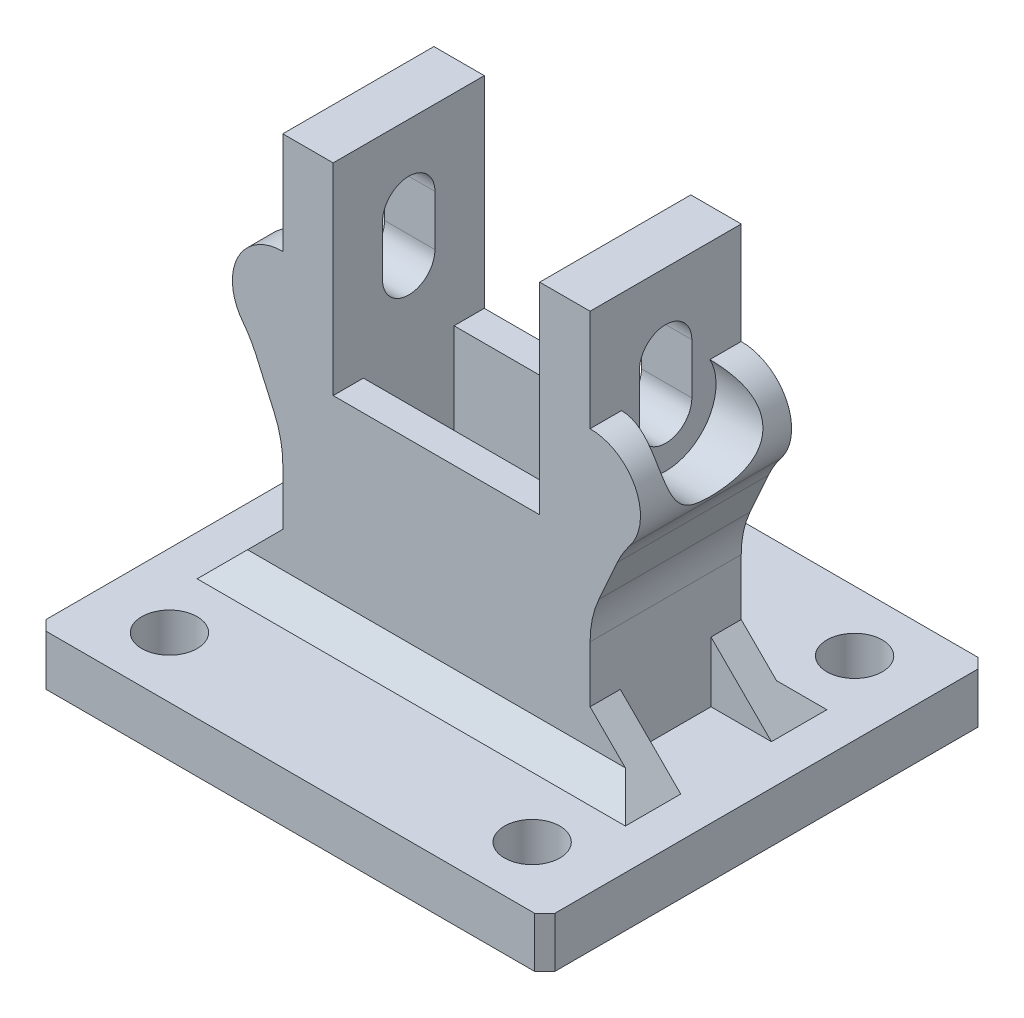
SolidWorks part; units mm, degrees
ref_plane "Front Plane" through (0, 0, 0) normal (0, 0, 1) x (1, 0, 0)
ref_plane "Top Plane" through (0, 0, 0) normal (0, 1, 0) x (1, 0, 0)
ref_plane "Right Plane" through (0, 0, 0) normal (1, 0, 0) x (0, 0, -1)
sketch "Sketch1" plane through (0, 0, 0) normal (0, 1, 0) x (1, 0, 0)
  line L1 (-18, 16) -> (18, 16) construction
  line L2 (-18, 16) -> (-18, -16) construction
  line L3 (-18, -16) -> (18, -16) construction
  line L4 (18, 16) -> (18, -16) construction
  line L5 (-18, 16) -> (18, -16) construction
  line L6 (-18, -16) -> (18, 16) construction
  line L7 (-25.25, 22) -> (25.25, 22)
  line L8 (-25.25, 22) -> (-25.25, -22)
  line L9 (-25.25, -22) -> (25.25, -22)
  line L10 (25.25, 22) -> (25.25, -22)
  line L11 (-25.25, 22) -> (25.25, -22) construction
  line L12 (-25.25, -22) -> (25.25, 22) construction
  circle A0 centre (-18, 16) radius 2.75
  circle A1 centre (18, 16) radius 2.75
  circle A2 centre (18, -16) radius 2.75
  circle A3 centre (-18, -16) radius 2.75
  point P0 (0, 0)
  point P10 (0, 0)
  dimension "D3" = 5.5
  dimension "D1" = 32
  dimension "D2" = 36
  dimension "D4" = 50.5
  dimension "D5" = 44
extrude "Boss-Extrude1" add sketch "Sketch1" along normal blind 5
sketch "Sketch3" plane through (0, 0, 22) normal (0, 0, 1) x (1, 0, 0)
  line L0 (-25.25, 5) -> (25.25, 5) construction
  line L1 (-15.25, 5) -> (-10.25, 5)
  line L2 (-15.25, 5) -> (-15.25, 45)
  line L3 (-15.25, 45) -> (-10.25, 45)
  line L4 (-10.25, 5) -> (-10.25, 45)
  line L6 (10.25, 5) -> (15.25, 5)
  line L7 (10.25, 5) -> (10.25, 45)
  line L8 (10.25, 45) -> (15.25, 45)
  line L9 (15.25, 5) -> (15.25, 45)
  line L10 (0, 0) -> (0, -8.4132) construction
  dimension "D1" = 5
  dimension "D2" = 20.5
  dimension "D3" = 40
extrude "Boss-Extrude2" add sketch "Sketch3" against normal blind 15 from offset 14.5 offset against normal yes
sketch "Sketch4" plane through (15.25, 0, 0) normal (1, 0, 0) x (0, 0, -1)
  line L0 (0, 37.5) -> (0, 32.5) construction
  line L1 (2.6, 37.5) -> (2.6, 32.5)
  line L2 (-2.6, 37.5) -> (-2.6, 32.5)
  line L3 (7.5, 45) -> (-7.5, 45) construction
  arc A0 (2.6, 37.5) -> (-2.6, 37.5) centre (0, 37.5) ccw
  arc A1 (-2.6, 32.5) -> (2.6, 32.5) centre (0, 32.5) ccw
  point P3 (0, 35)
  dimension "D2" = 2.6
  dimension "D1" = 5
  dimension "D3" = 10
extrude "Cut-Extrude1" cut sketch "Sketch4" against normal up to surface (30.5 mm away) up to face at (-15.25, 25, 0)
sketch "Sketch5" plane through (0, 0, 7.5) normal (0, 0, 1) x (1, 0, 0)
  line L0 (15.25, 11) -> (21.25, 5)
  line L1 (15.25, 5) -> (15.25, 45) construction
  line L2 (-25.25, 5) -> (25.25, 5) construction
  line L3 (21.25, 5) -> (15.25, 5)
  line L4 (15.25, 5) -> (15.25, 11)
  line L5 (0, -1.6344) -> (0, 7.9357) construction
  line L6 (-21.25, 5) -> (-15.25, 5)
  line L7 (-15.25, 11) -> (-21.25, 5)
  line L8 (-15.25, 5) -> (-15.25, 11)
  line L17 (-10.25, 5) -> (-10.25, 45) construction
  line L18 (-10.25, 25) -> (10.25, 25)
  line L19 (-10.25, 25) -> (-10.25, 5)
  line L20 (-10.25, 5) -> (10.25, 5)
  line L21 (10.25, 25) -> (10.25, 5)
  dimension "D1" = 45
  dimension "D2" = 6
  dimension "D3" = 20
extrude "Boss-Extrude3" add sketch "Sketch5" against normal blind 3
ref_plane "Plane1" through (0, 0, 0) normal (0, 0, -1) x (-1, 0, 0)
mirror "Mirror1" about plane through (0, 0, 0) normal (0, 0, -1) of "Boss-Extrude3"
chamfer "Chamfer2" distance 1 angle 45 4 edges at (25.25, 2.5, 22) (-25.25, 2.5, -22) (25.25, 2.5, -22) (-25.25, 2.5, 22)
chamfer "Chamfer3" distance 2.5 angle 45 2 edges at (0, 5, -7.5) (0, 5, 7.5)
sketch "Sketch6" plane through (0, 0, 7.5) normal (0, 0, 1) x (1, 0, 0)
  line L0 (15.25, 29.9) -> (15.25, 32.5) construction
  line L1 (15.25, 29.9) -> (15.25, 32.5) construction
  line L2 (-15.25, 32.5) -> (-15.25, 29.9) construction
  line L3 (-15.25, 32.5) -> (-15.25, 29.9) construction
  line L4 (-15.25, 45) -> (-15.25, 11) construction
  line L5 (-15.25, 34.9) -> (-15.25, 24.9)
  line L6 (0, 16.2237) -> (0, 26.731) construction
  line L7 (-24.25, 0) -> (24.25, 0) construction
  line L8 (15.25, 34.9) -> (15.25, 24.9)
  arc A0 (-15.25, 34.9) -> (-15.25, 24.9) centre (-15.25, 29.9) ccw
  arc A1 (15.25, 34.9) -> (15.25, 24.9) centre (15.25, 29.9) cw
  point P13 (0, 0)
  dimension "D1" = 5
extrude "Boss-Extrude4" add sketch "Sketch6" against normal up to surface (15 mm away) up to face at (0, 26.7, -7.5)
sketch "Sketch7" plane through (-10.25, 0, 0) normal (1, 0, 0) x (0, 0, -1)
  circle A0 centre (0, 32.5) radius 5
  arc A1 (-2.6, 32.5) -> (2.6, 32.5) centre (0, 32.5) ccw construction
  point P5 (3.1044, 30.5539)
  dimension "D1" = 10
extrude "Cut-Extrude2" cut sketch "Sketch7" against normal up to surface (4.2708 mm away) from surface up to face at (-16.9167, 31.5667, 0) starting at face at (-15.25, 38.4, 0)
extrude "Cut-Extrude3" cut sketch "Sketch7<2>" along normal up to surface from surface up to face at (16.9167, 31.5667, 0) starting at face at (15.25, 38.4, 0)
sketch "Sketch7<2>" plane through (-10.25, 0, 0) normal (1, 0, 0) x (0, 0, -1) same geometry as "Sketch7"
chamfer "Chamfer4" distance 10 angle 45 2 edges at (-15.25, 24.9, 0) (15.25, 24.9, 0)
fillet "Fillet1" radius 10 4 edges at (18.5833, 26.1732, 0) (-18.5833, 26.1732, 0) (-15.25, 18.7197, 0) (15.25, 18.7197, 0)
